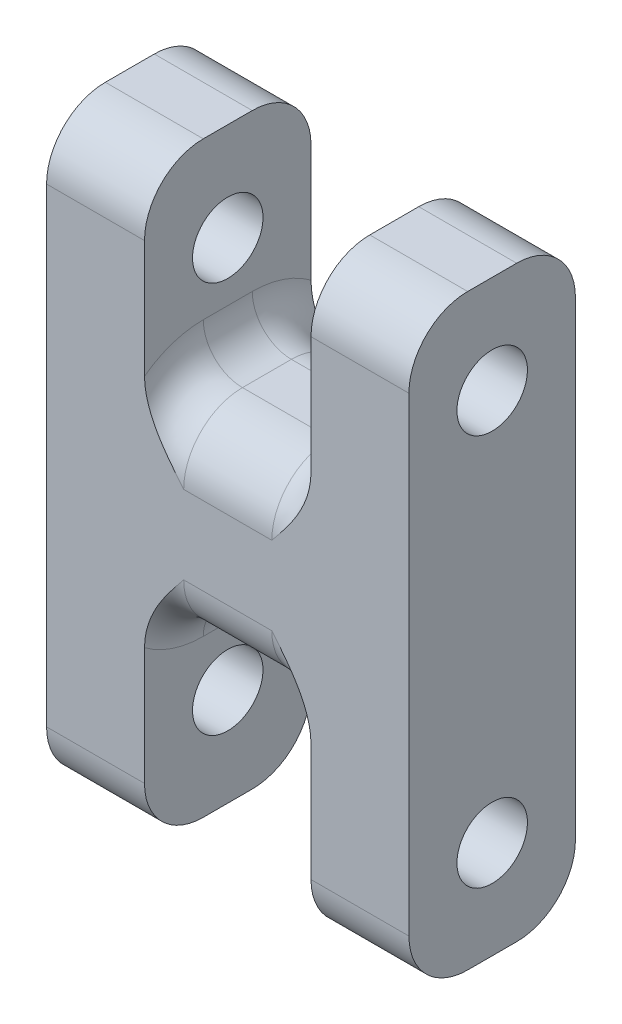
SolidWorks part; units mm, degrees
ref_plane "Plan de face" through (0, 0, 0) normal (0, 0, 1) x (1, 0, 0)
ref_plane "Plan de dessus" through (0, 0, 0) normal (0, 1, 0) x (1, 0, 0)
ref_plane "Plan de droite" through (0, 0, 0) normal (1, 0, 0) x (0, 0, -1)
sketch "Esquisse1" plane through (0, 0, 0) normal (0, 0, 1) x (1, 0, 0)
  line L0 (0, 30) -> (0, 0)
  line L1 (0, 30) -> (5, 30)
  line L2 (0, 0) -> (5, 0)
  line L3 (5, 30) -> (5, 0)
  line L4 (18.5, 30) -> (13.5, 30)
  line L5 (18.5, 30) -> (18.5, 0)
  line L6 (13.5, 30) -> (13.5, 0)
  line L7 (18.5, 0) -> (13.5, 0)
  line L8 (5, 20) -> (13.5, 20)
  line L9 (5, 20) -> (5, 10)
  line L10 (13.5, 20) -> (13.5, 10)
  line L11 (5, 10) -> (13.5, 10)
  line L15 (5, 25) -> (5, 5)
  line L19 (0, 20) -> (0, 10)
  dimension "D2" = 10
  dimension "D3" = 10
  dimension "D4" = 5
  dimension "D5" = 5
  dimension "D6" = 30
  dimension "D13" = 18.5
extrude "Boss.-Extru.1" add sketch "Esquisse1" along normal blind 8.5 contours L15 L8 | L8 L19 L11 L15 | L15 L11 | L8 L11 | L8 L3 L11 | L8 L15 L11 L6 | L7 L5 L4 L6 | L3 L1 L0 L2 region at (2.5, 15, 0) region at (9.25, 15, 0) region at (16, 15, 0)
sketch "Esquisse2" plane through (18.5, 0, 0) normal (1, 0, 0) x (0, 0, -1)
  line L1 (-8.5, 30) -> (0, 30) construction
  line L2 (-4.25, 30) -> (-4.25, 0) construction
  line L3 (-8.5, 0) -> (0, 0) construction
  circle A0 centre (-4.25, 25) radius 1.8
  circle A1 centre (-4.25, 5) radius 1.8
  point P10 (-4.5, 5.1085)
  point P11 (-4.5, 25)
  dimension "D1" = 3.6
  dimension "D3" = 3.6
  dimension "D5" = 20
  dimension "D6" = 5
extrude "Enlèv. mat.-Extru.1" cut sketch "Esquisse2" against normal blind 20
fillet "Congé3" radius 3 12 edges at (16, 30, 8.5) (2.5, 30, 8.5) (2.5, 0, 8.5) (16, 0, 8.5) (16, 0, 0) (9.25, 20, 0) (9.25, 10, 0) (9.25, 20, 8.5) (9.25, 10, 8.5) (16, 30, 0) (2.5, 30, 0) (2.5, 0, 0) tangent propagation no
fillet "Congé1" radius 2 12 edges at (13.5, 10, 4.25) (5, 10, 4.25) (13.5, 20, 4.25) (5, 20, 4.25) (13.5, 10.8787, 7.6213) (13.5, 10.8787, 0.8787) (5, 10.8787, 7.6213) (5, 10.8787, 0.8787) (13.5, 19.1213, 7.6213) (13.5, 19.1213, 0.8787) (5, 19.1213, 7.6213) (5, 19.1213, 0.8787)
